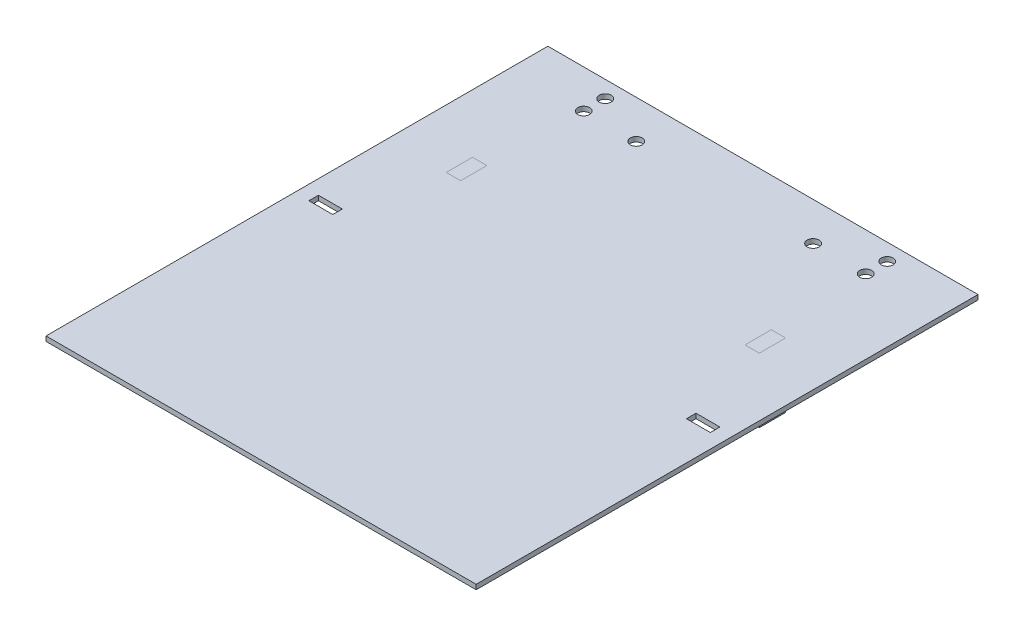
SolidWorks part; units mm, degrees
material "ABS"
ref_plane "Front Plane" through (0, 0, 0) normal (0, 0, 1) x (1, 0, 0)
ref_plane "Top Plane" through (0, 0, 0) normal (0, 1, 0) x (1, 0, 0)
ref_plane "Right Plane" through (0, 0, 0) normal (1, 0, 0) x (0, 0, -1)
sketch "Sketch1" plane through (0, 0, 0) normal (0, 1, 0) x (1, 0, 0)
  line L1 (90, 105) -> (-90, 105)
  line L2 (90, 105) -> (90, -105)
  line L3 (90, -105) -> (-90, -105)
  line L4 (-90, 105) -> (-90, -105)
  line L5 (90, 105) -> (-90, -105) construction
  line L6 (90, -105) -> (-90, 105) construction
  line L11 (84, 3) -> (74, 3)
  line L12 (84, 3) -> (84, -1)
  line L13 (84, -1) -> (74, -1)
  line L14 (74, 3) -> (74, -1)
  line L15 (84, 3) -> (74, -1) construction
  line L16 (84, -1) -> (74, 3) construction
  line L17 (-84, -1) -> (-74, -1)
  line L18 (-84, -1) -> (-84, 3)
  line L19 (-84, 3) -> (-74, 3)
  line L20 (-74, -1) -> (-74, 3)
  line L21 (-84, -1) -> (-74, 3) construction
  line L22 (-84, 3) -> (-74, -1) construction
  line L23 (-65.5, 38) -> (-59.5, 38)
  line L24 (-65.5, 38) -> (-65.5, 49)
  line L25 (-65.5, 49) -> (-59.5, 49)
  line L26 (-59.5, 38) -> (-59.5, 49)
  line L27 (-65.5, 38) -> (-59.5, 49) construction
  line L28 (-65.5, 49) -> (-59.5, 38) construction
  line L29 (59.5, 38) -> (65.5, 38)
  line L30 (59.5, 38) -> (59.5, 49)
  line L31 (59.5, 49) -> (65.5, 49)
  line L32 (65.5, 38) -> (65.5, 49)
  line L33 (59.5, 38) -> (65.5, 49) construction
  line L34 (59.5, 49) -> (65.5, 38) construction
  circle A0 centre (-59, 98) radius 2.5
  circle A1 centre (-59, 89) radius 2.5
  circle A2 centre (-37, 89) radius 2.5
  circle A3 centre (59, 98) radius 2.5
  circle A4 centre (59, 89) radius 2.5
  circle A5 centre (37, 89) radius 2.5
  point P0 (0, 0)
  point P6 (79, 1)
  point P23 (-79, 1)
  point P28 (-62.5, 43.5)
  point P33 (62.5, 43.5)
  dimension "D7" = 16
  dimension "D8" = 53
  dimension "D9" = 16
  dimension "D11" = 7
  dimension "D13" = 31
  dimension "D15" = 53
  dimension "D17" = 10
  dimension "D1" = 180
  dimension "D2" = 210
  dimension "D3" = 31
  dimension "D4" = 31
  dimension "D5" = 7
  dimension "D6" = 104
  dimension "D10" = 16
  dimension "D12" = 16
  dimension "D14" = 31
  dimension "D16" = 6
  dimension "D18" = 4
  dimension "D19" = 104
  dimension "D20" = 6
  dimension "D21" = 4
  dimension "D22" = 10
  dimension "D23" = 56
  dimension "D24" = 24.5
  dimension "D25" = 11
  dimension "D26" = 6
  dimension "D27" = 56
  dimension "D28" = 6
  dimension "D29" = 11
  dimension "D30" = 24.5
extrude "MainBody" add sketch "Sketch1" along normal blind 2
extrude "SayapRoda" add sketch "Sketch1<4>" against normal blind 25 and the other way blind 2 separate body contours L23 L26 L25 L24 | L29 L32 L31 L30 region at (-62.5, 0, -43.5) region at (62.5, 0, -43.5)
sketch "Sketch1<4>" plane through (0, 0, 0) normal (0, 1, 0) x (1, 0, 0) same geometry as "Sketch1"
hole_wizard "Hole1" positions "3DSketch2" profile "Sketch9" legacy end condition through all
sketch3d "3DSketch2"
  line L0 (65.5, 2, -49) -> (65.5, -25, -49) construction
  point P0 (65.5, -20.2331, -43.5)
  point P2 (65.5, -9.2332, -43.4453)
  point P4 (65.5, -7.7287, -43.5)
  point P6 (65.5, -6.2408, -43.5)
  point P8 (65.5, -4.8783, -43.5)
  dimension "D1" = 11
  dimension "D2" = 5.5
  dimension "D3" = 5.5
  dimension "D4" = 5.5
  dimension "D5" = 5.5
sketch "Sketch9" plane through (65.5, -20.2331, -43.5) normal (0, 1, 0) x (0, 0, -1)
  line L0 (0, 0) -> (0, 155.5)
  line L1 (0, 155.5) -> (1.5, 155.5)
  line L2 (1.5, 155.5) -> (1.5, 0)
  line L3 (1.5, 0) -> (0, 0)
  line L4 (0, 110) -> (0, -10) construction
  dimension "Diameter" = 3
  dimension "Depth" = 155.5
